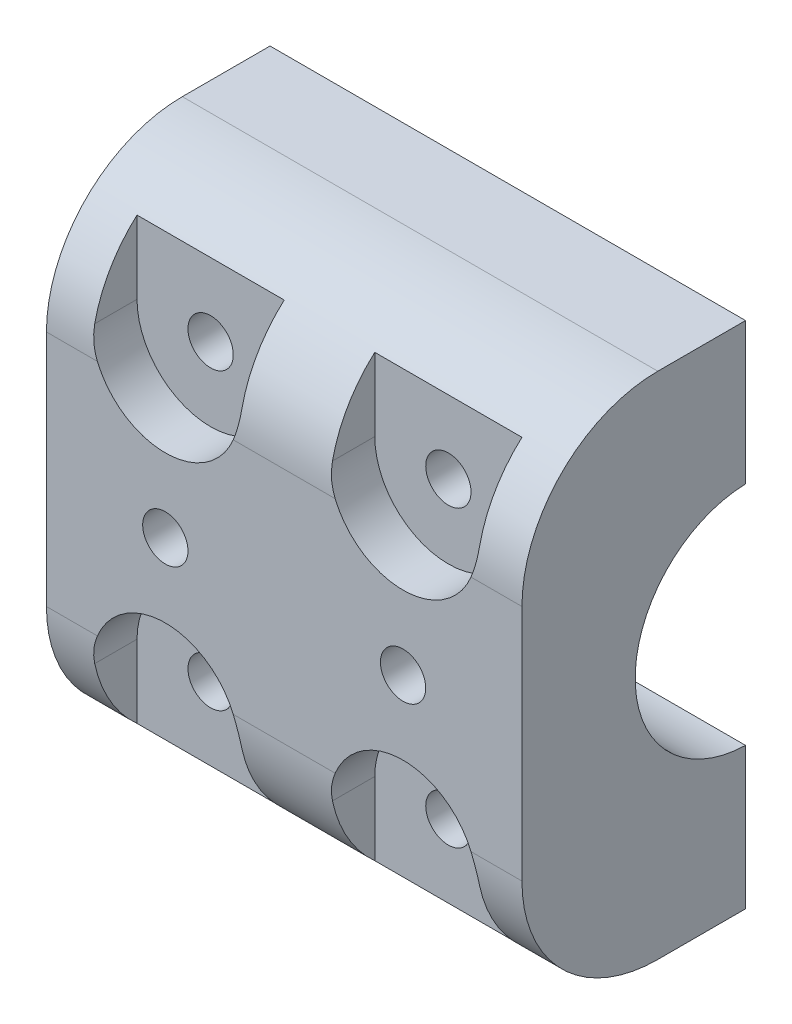
SolidWorks part; units mm, degrees
ref_plane "Front Plane" through (0, 0, 0) normal (0, 0, 1) x (1, 0, 0)
ref_plane "Top Plane" through (0, 0, 0) normal (0, 1, 0) x (1, 0, 0)
ref_plane "Right Plane" through (0, 0, 0) normal (1, 0, 0) x (0, 0, -1)
sketch "Sketch1" plane through (0, 0, 0) normal (1, 0, 0) x (0, 0, -1)
  line L0 (0, 22.5) -> (0, -22.5) construction
  line L1 (-0.25, 22.5) -> (-0.25, 9.9969)
  line L2 (-0.25, -9.9969) -> (-0.25, -22.5)
  line L4 (-0.25, 22.5) -> (-0.25, -22.5) construction
  line L6 (-20, 10.5) -> (-20, -10.5)
  line L8 (0, 22.5) -> (-3, 22.5)
  line L9 (-3, 22.5) -> (-8, 22.5)
  line L10 (0, 0) -> (-22.5, 0) construction
  line L11 (-3, -22.5) -> (-8, -22.5)
  line L12 (0, -22.5) -> (-3, -22.5)
  arc A0 (0, 22.5) -> (0, -22.5) centre (0, 0) ccw construction
  arc A1 (0, 10) -> (0, -10) centre (0, 0) ccw
  circle A3 centre (0, 0) radius 10 construction
  arc A7 (-8, 22.5) -> (-20, 10.5) centre (-8, 10.5) ccw
  arc A8 (-8, -22.5) -> (-20, -10.5) centre (-8, -10.5) cw
  dimension "D2" = 45
  dimension "D3" = 20
  dimension "D4" = 3
  dimension "D5" = 5
  dimension "D1" = 0.25
extrude "Boss-Extrude1" add sketch "Sketch1" against normal blind 42 contours A1 L1 A0 L2 region at (0, 0, 10.7608)
sketch "Sketch2" plane through (0, 0, 0.25) normal (0, 0, 1) x (1, 0, 0)
  line L0 (0, 0) -> (-42, 0) construction
  line L1 (-42, -22.5) -> (0, -22.5) construction
  line L2 (-42, 13) -> (-21, 13) construction
  line L3 (-10.5, 11) -> (-31.5, 11) construction
  line L5 (-21, 22.5) -> (-21, -22.5) construction
  line L6 (-42, 22.5) -> (-42, 10.5) construction
  line L7 (-42, 10.5) -> (-42, -10.5) construction
  line L11 (-42, 22.5) -> (0, 22.5) construction
  circle A0 centre (-31.5, 13) radius 2
  circle A1 centre (-10.5, 13) radius 2
  circle A2 centre (-10.5, -13) radius 2
  circle A3 centre (-31.5, -13) radius 2
  point P21 (-21, 11)
  dimension "D2" = 4
  dimension "D1" = 13
extrude "Cut-Extrude2" cut sketch "Sketch2" along normal through all contours A1 | A0 | A3 | A2 region at (-31.5, 13, 0.25) region at (-10.5, 13, 0.25) region at (-10.5, -13, 0.25) region at (-31.5, -13, 0.25)
sketch "Sketch3" plane through (0, 0, 20) normal (0, 0, 1) x (1, 0, 0)
  line L0 (0, 0) -> (-42, 0) construction
  line L2 (-38, 13) -> (-38, 19.5)
  line L3 (-38, 19.5) -> (-25, 19.5)
  line L4 (-25, 19.5) -> (-25, 13)
  line L5 (-17, 13) -> (-17, 19.5)
  line L6 (-17, 19.5) -> (-4, 19.5)
  line L7 (-4, 19.5) -> (-4, 13)
  line L8 (-4, -19.5) -> (-4, -13)
  line L9 (-17, -19.5) -> (-4, -19.5)
  line L10 (-17, -13) -> (-17, -19.5)
  line L11 (-25, -19.5) -> (-25, -13)
  line L12 (-38, -19.5) -> (-25, -19.5)
  line L13 (-38, -13) -> (-38, -19.5)
  line L14 (-42, 10.5) -> (-42, -10.5) construction
  arc A0 (-38, 13) -> (-25, 13) centre (-31.5, 13) ccw
  arc A1 (-17, 13) -> (-4, 13) centre (-10.5, 13) ccw
  arc A2 (-17, -13) -> (-4, -13) centre (-10.5, -13) cw
  arc A3 (-38, -13) -> (-25, -13) centre (-31.5, -13) cw
  dimension "D1" = 13
extrude "Cut-Extrude3" cut sketch "Sketch3" against normal blind 4
sketch "Sketch4" plane through (0, 0, 20) normal (0, 0, 1) x (1, 0, 0)
  circle A0 centre (-10.5, 0) radius 2
  circle A1 centre (-31.5, 0) radius 2
  circle A2 centre (-10.5, 0) radius 2 construction
extrude "Cut-Extrude4" cut sketch "Sketch4" against normal through all
